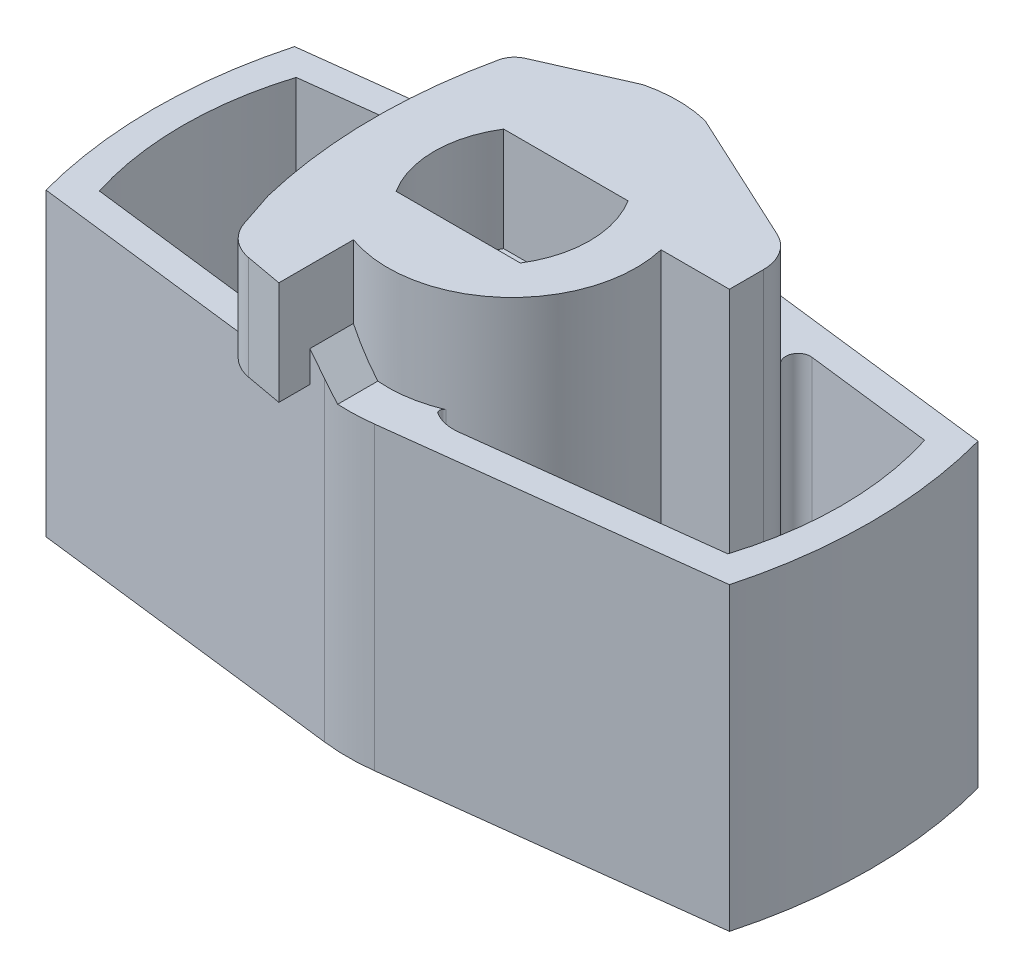
SolidWorks part; units mm, degrees
ref_plane "Front Plane" through (0, 0, 0) normal (0, 0, 1) x (1, 0, 0)
ref_plane "Top Plane" through (0, 0, 0) normal (0, 1, 0) x (1, 0, 0)
ref_plane "Right Plane" through (0, 0, 0) normal (1, 0, 0) x (0, 0, -1)
sketch "Sketch1" plane through (0, 0, 0) normal (0, 1, 0) x (1, 0, 0)
  line L0 (0, 0) -> (16.5, -2)
  line L1 (16.5, -2) -> (33, 0)
  line L2 (0, 12) -> (16.5, 14)
  line L3 (16.5, 14) -> (33, 12)
  line L4 (1.3263, 10.7505) -> (16.5, 12.5898)
  line L5 (16.5, 12.5898) -> (31.6737, 10.7505)
  line L6 (1.3263, 1.2495) -> (16.5, -0.5898)
  line L7 (16.5, -0.5898) -> (31.6737, 1.2495)
  arc A0 (0, 0) -> (0, 12) centre (22.1, 6) cw
  arc A2 (33, 12) -> (33, 0) centre (10.9, 6) cw
  arc A3 (1.3263, 10.7505) -> (1.3263, 1.2495) centre (16.5, 6) ccw
  arc A4 (31.6737, 10.7505) -> (31.6737, 1.2495) centre (16.5, 6) cw
  circle A5 centre (16.5, 6) radius 15.9 construction
  circle A6 centre (16.5, 6) radius 2
  point P14 (33.8, 6)
  point P15 (-0.8, 6)
  dimension "D7" = 31.8
  dimension "D9" = 4
  dimension "D1" = 16
  dimension "D2" = 33
  dimension "D3" = 12
  dimension "D4" = 12
  dimension "D5" = 34.6
  dimension "D6" = 1.4
  dimension "D8" = 1.4
extrude "Boss-Extrude1" add sketch "Sketch1" along normal blind 14.5 contours A2 L3 L2 A0 L0 L1 L5 A4 L7 L6 A3 L4 region at (-0.4188, 0, -6)
extrude "Boss-Extrude2" add sketch "Sketch1<3>" along normal blind 2 contours A4 L5 L4 A3 L6 L7 A6 region at (8.9545, 0, -11.3284)
sketch "Sketch1<3>" plane through (0, 0, 0) normal (0, 1, 0) x (1, 0, 0) same geometry as "Sketch1"
sketch "Sketch2" plane through (0, 2, 0) normal (0, 1, 0) x (1, 0, 0)
  line L0 (22.3459, 7.3512) -> (25.6459, 7.3512)
  line L1 (25.6459, 7.3512) -> (25.6459, 10.2724)
  line L2 (25.6459, 10.2724) -> (18, 13.8182)
  line L3 (15, 13.8182) -> (10.6, 11.8746)
  line L4 (1.3263, 1.2495) -> (16.5, -0.5898) construction
  line L5 (10.6, 0.1254) -> (14.5, -1.7576)
  line L6 (14.5, -1.7576) -> (18.5, -1.7576)
  line L7 (18.5, -1.7576) -> (18.5, 0.3431)
  line L8 (16.5, 14) -> (33, 12) construction
  line L9 (0, 12) -> (16.5, 14) construction
  line L10 (18.5, 6) -> (18.5, 0.3431) construction
  line L11 (16.5, 12.5898) -> (31.6737, 10.7505) construction
  line L12 (16.5, 14) -> (33, 12) construction
  line L13 (1.3263, 10.7505) -> (16.5, 12.5898) construction
  line L14 (16.5, -2) -> (33, 0) construction
  line L15 (0, 0) -> (16.5, -2) construction
  circle A0 centre (16.5, 6) radius 6 construction
  arc A1 (18, 13.8182) -> (15, 13.8182) centre (16.5, 7.7216) ccw
  arc A3 (18.5, 0.3431) -> (22.3459, 7.3512) centre (16.5, 6) ccw
  arc A4 (10.6, 0.1254) -> (10.6, 11.8746) centre (34.9007, 6) cw
  circle A5 centre (16.5, 6) radius 2
  circle A7 centre (16.5, 6) radius 2 construction
  point P10 (9.9, 6)
  point P27 (16.5, 14)
  dimension "D1" = 12
  dimension "D2" = 3
  dimension "D3" = 1.2
  dimension "D4" = 3.3
  dimension "D5" = 5.5
  dimension "D6" = 6.6
  dimension "D7" = 5.9
extrude "Boss-Extrude3" add sketch "Sketch2" along normal up to surface (12.5 mm away) up to face at (16.5, 14.5, -6)
extrude "Boss-Extrude4" add sketch "Sketch2<2>" against normal up to surface (2 mm away) up to face at (16.5, 0, -6)
sketch "Sketch2<2>" plane through (0, 2, 0) normal (0, 1, 0) x (1, 0, 0) same geometry as "Sketch2"
sketch "Sketch3" plane through (0, 14.5, 0) normal (0, 1, 0) x (1, 0, 0)
  line L0 (22.3459, 7.3512) -> (25.6459, 7.3512)
  line L1 (25.6459, 7.3512) -> (25.6459, 10.2724)
  line L2 (25.6459, 10.2724) -> (18, 13.8182)
  line L3 (15, 13.8182) -> (10.6, 11.8746)
  line L4 (14.5, 0.3431) -> (14.5, -3.2569)
  line L5 (14.5, -3.2569) -> (12.7139, -2.9325)
  line L6 (11.1738, -1.5969) -> (10.6, 0.1254)
  line L7 (14.5, 0.3431) -> (14.5, 6) construction
  line L8 (13.5, 8.6) -> (19.5, 8.6)
  line L9 (19.5, 3.4) -> (13.5, 3.4)
  arc A0 (14.5, 0.3431) -> (22.3459, 7.3512) centre (16.5, 6) ccw
  arc A1 (10.6, 0.1254) -> (10.6, 11.8746) centre (34.9007, 6) cw
  arc A2 (18, 13.8182) -> (15, 13.8182) centre (16.5, 7.7216) ccw
  arc A3 (18, 13.8182) -> (15, 13.8182) centre (16.5, 7.7216) ccw construction
  arc A4 (10.6, 11.8746) -> (10.6, 0.1254) centre (34.9007, 6) ccw construction
  arc A5 (18.5, 0.3431) -> (22.3459, 7.3512) centre (16.5, 6) ccw construction
  circle A6 centre (16.5, 6) radius 2 construction
  arc A7 (12.7139, -2.9325) -> (11.1738, -1.5969) centre (13.0713, -0.9647) cw
  arc A8 (13.5, 3.4) -> (13.5, 8.6) centre (17.6317, 6) cw
  arc A9 (19.5, 3.4) -> (19.5, 8.6) centre (15.3683, 6) ccw
  point P4 (16.5, 8.6)
  point P38 (11.5483, -2.7208)
  point P41 (20.25, 6)
  point P42 (16.5, 3.4)
  point P44 (12.75, 6)
  dimension "D4" = 2
  dimension "D1" = 3.6
  dimension "D2" = 3
  dimension "D3" = 3
  dimension "D5" = 6
  dimension "D6" = 7.5
  dimension "D7" = 5.2
extrude "Boss-Extrude5" add sketch "Sketch3" along normal blind 5
chamfer "Chamfer1" distance 1.5 angle 45 1 edges at (14.5, 14.5, 0.7072)
fillet "Fillet3" radius 2 1 edges at (25.6459, 10.75, -10.2724)
fillet "Fillet1" radius 0.6 1 edges at (22.117, 8.25, -11.9089)
fillet "Fillet4" radius 2 1 edges at (18.5, 8.25, 0.3473)
fillet "Fillet5" radius 0.2 1 edges at (18.5, 8.25, -0.3431)
fillet "Fillet6" radius 1 1 edges at (10.6, 17, -11.8746)
fillet "Fillet7" radius 10 1 edges at (16.5, 7.25, 2)
